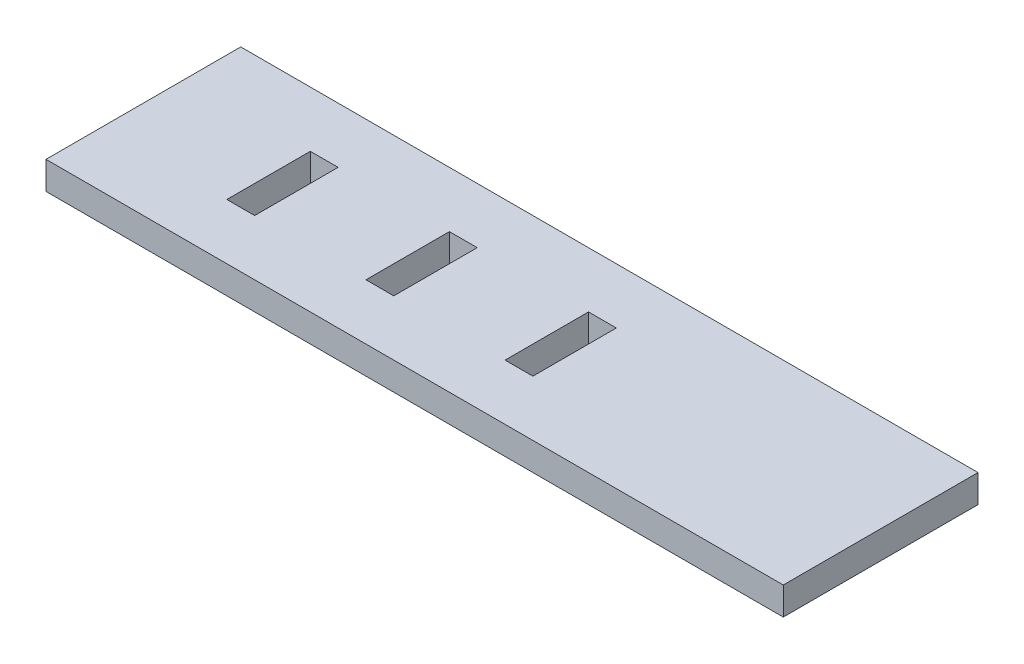
SolidWorks part; units mm, degrees
ref_plane "Front Plane" through (0, 0, 0) normal (0, 0, 1) x (1, 0, 0)
ref_plane "Top Plane" through (0, 0, 0) normal (0, 1, 0) x (1, 0, 0)
ref_plane "Right Plane" through (0, 0, 0) normal (1, 0, 0) x (0, 0, -1)
sketch "Sketch1" plane through (0, 0, 0) normal (0, 1, 0) x (1, 0, 0)
  line L0 (-98.4247, 8.4932) -> (-48.4247, 8.4932) construction
  line L1 (-98.4247, 43.4932) -> (166.5753, 43.4932)
  line L2 (-98.4247, 43.4932) -> (-98.4247, -26.5068)
  line L3 (-98.4247, -26.5068) -> (166.5753, -26.5068)
  line L4 (166.5753, 43.4932) -> (166.5753, -26.5068)
  line L5 (-98.4247, 8.4932) -> (1.5753, 8.4932) construction
  line L6 (-53.4247, 23.4932) -> (-43.4247, 23.4932)
  line L7 (-53.4247, 23.4932) -> (-53.4247, -6.5068)
  line L8 (-53.4247, -6.5068) -> (-43.4247, -6.5068)
  line L9 (-43.4247, 23.4932) -> (-43.4247, -6.5068)
  line L10 (-53.4247, 23.4932) -> (-43.4247, -6.5068) construction
  line L11 (-53.4247, -6.5068) -> (-43.4247, 23.4932) construction
  line L12 (-98.4247, 8.4932) -> (54.9772, 8.4932) construction
  line L13 (6.5753, 23.4932) -> (-3.4247, 23.4932)
  line L14 (6.5753, 23.4932) -> (6.5753, -6.5068)
  line L15 (6.5753, -6.5068) -> (-3.4247, -6.5068)
  line L16 (-3.4247, 23.4932) -> (-3.4247, -6.5068)
  line L17 (6.5753, 23.4932) -> (-3.4247, -6.5068) construction
  line L18 (6.5753, -6.5068) -> (-3.4247, 23.4932) construction
  line L21 (46.5753, 23.4932) -> (56.5753, 23.4932)
  line L22 (46.5753, 23.4932) -> (46.5753, -6.5068)
  line L23 (46.5753, -6.5068) -> (56.5753, -6.5068)
  line L24 (56.5753, 23.4932) -> (56.5753, -6.5068)
  line L25 (46.5753, 23.4932) -> (56.5753, -6.5068) construction
  line L26 (46.5753, -6.5068) -> (56.5753, 23.4932) construction
  dimension "D1" = 70
  dimension "D2" = 265
  dimension "D3" = 50
  dimension "D4" = 10
  dimension "D5" = 30
  dimension "D6" = 100
  dimension "D7" = 10
  dimension "D8" = 30
  dimension "D9" = 10
  dimension "30" = 30
extrude "Boss-Extrude1" add sketch "Sketch1" along normal blind 10
